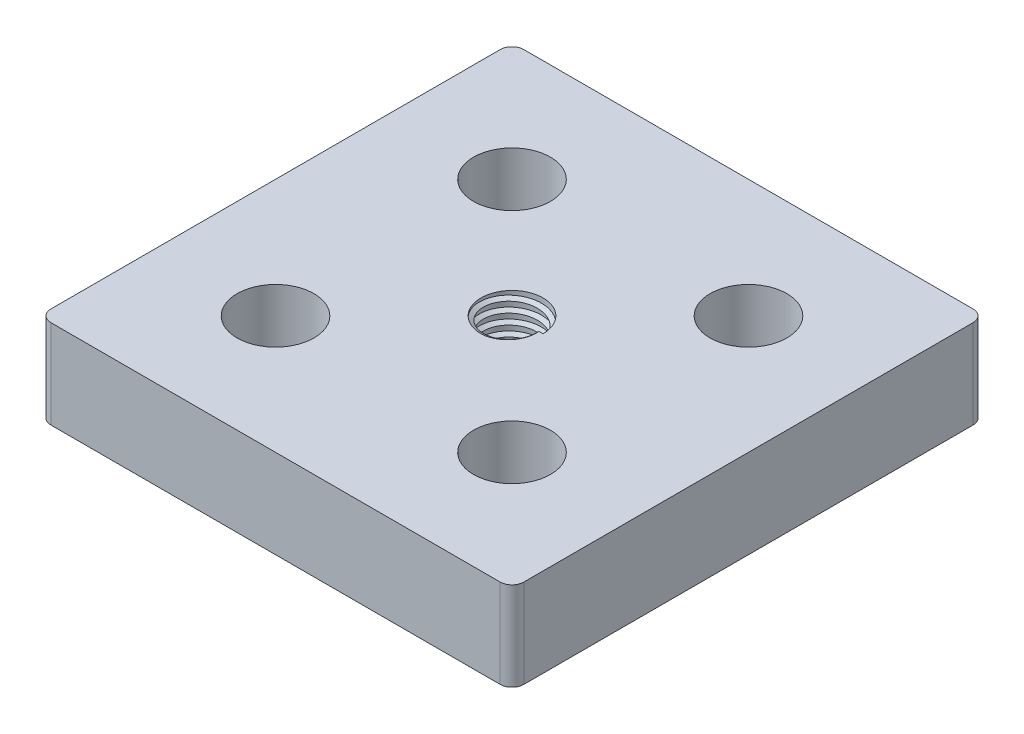
SolidWorks part; units mm, degrees
ref_plane "前视基准面" through (0, 0, 0) normal (0, 0, 1) x (1, 0, 0)
ref_plane "上视基准面" through (0, 0, 0) normal (0, 1, 0) x (1, 0, 0)
ref_plane "右视基准面" through (0, 0, 0) normal (1, 0, 0) x (0, 0, -1)
sketch "草图1" plane through (0, 0, 0) normal (0, 1, 0) x (1, 0, 0)
  line B0 (-38, -40) -> (38, -40)
  line B1 (40, -38) -> (40, 38)
  line B2 (38, 40) -> (-38, 40)
  line B3 (-40, 38) -> (-40, -38)
  arc B4 (38, -40) -> (40, -38) centre (38, -38) ccw
  arc B5 (40, 38) -> (38, 40) centre (38, 38) ccw
  arc B6 (-38, 40) -> (-40, 38) centre (-38, 38) ccw
  arc B7 (-40, -38) -> (-38, -40) centre (-38, -38) ccw
  circle B8 centre (-20, 20) radius 4.5
  circle B9 centre (-20, -20) radius 4.5
  circle B10 centre (20, -20) radius 4.5
  circle B11 centre (20, 20) radius 4.5
  circle B12 centre (0, 0) radius 5.25
sketch_block_instance "A$C31D36E24-1"
sketch_block "A$C31D36E24"
extrude "凸台-拉伸1" add sketch "草图1" along normal blind 15
sketch "草图3" plane through (0, 15, 0) normal (0, 1, 0) x (1, 0, 0)
  circle A0 centre (-20, 20) radius 6.5
  circle A1 centre (20, 20) radius 6.5
  circle A2 centre (20, -20) radius 6.5
  circle A3 centre (-20, -20) radius 6.5
  point P12 (0, 0)
  dimension "D1" = 4
extrude "切除-拉伸1" cut sketch "草图3" against normal blind 10
sketch "草图4" plane through (0, 15, 0) normal (0, 1, 0) x (1, 0, 0)
  circle A0 centre (0, 0) radius 5.25
curve "螺旋线/涡状线1" pitch 1.75 height 15 radius 5.25 centre (0, 15, 0) axis (0, -1, 0) start towards (1, 0, 0)
ref_plane "基准面2" through (5.25, 15, 0) normal (0, -0.053, 0.9986) x (1, 0, 0)
sketch "草图5" plane through (5.25, 15, 0) normal (0, -0.053, 0.9986) x (1, 0, 0)
  line L1 (-0.6914, 0) -> (0.3457, -0.5988)
  line L2 (0.3457, -0.5988) -> (0.3457, 0.5988)
  line L3 (0.3457, 0.5988) -> (-0.6914, 0)
sweep "扫描1" add profiles "草图5" path "螺旋线/涡状线1"
sketch "草图6" plane through (-40, 0, 0) normal (-1, 0, 0) x (0, 0, 1)
  line L1 (-40, 15) -> (43.619, 15)
  line L2 (-40, 15) -> (-40, 25.3999)
  line L3 (-40, 25.3999) -> (43.619, 25.3999)
  line L4 (43.619, 15) -> (43.619, 25.3999)
  line L5 (-40, 0) -> (41.9099, 0)
  line L6 (-40, 0) -> (-40, -15.2467)
  line L7 (-40, -15.2467) -> (41.9099, -15.2467)
  line L8 (41.9099, 0) -> (41.9099, -15.2467)
extrude "切除-拉伸2" cut sketch "草图6" against normal through all
